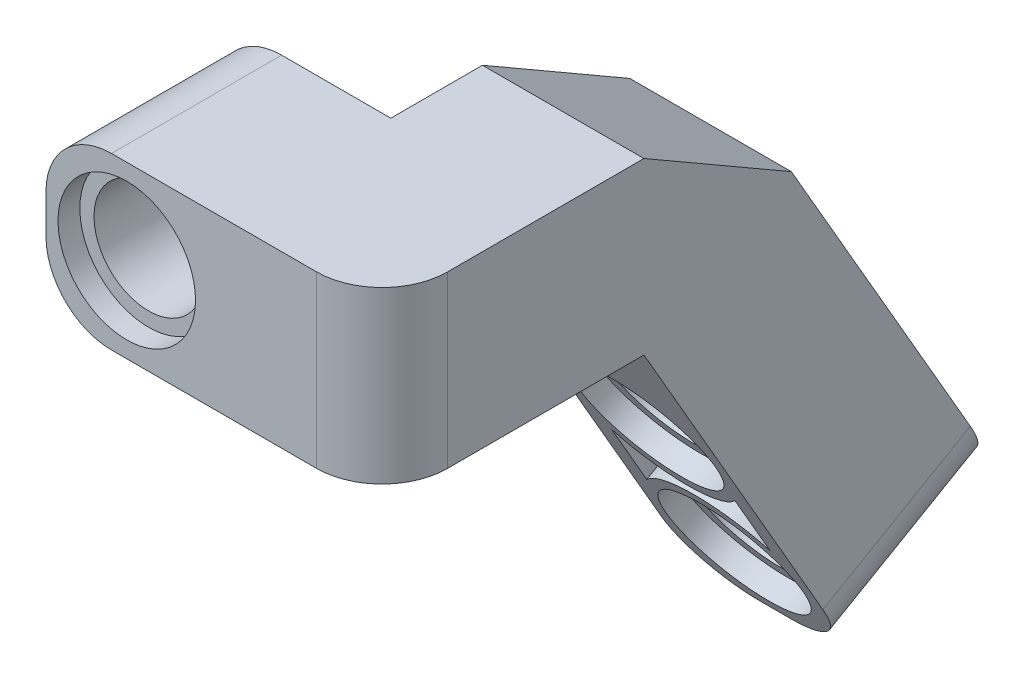
SolidWorks part; units mm, degrees
ref_plane "前视基准面" through (0, 0, 0) normal (0, 0, 1) x (1, 0, 0)
ref_plane "上视基准面" through (0, 0, 0) normal (0, 1, 0) x (1, 0, 0)
ref_plane "右视基准面" through (0, 0, 0) normal (1, 0, 0) x (0, 0, -1)
other "Configuration Table"
sketch "草图1" plane through (0, 0, 0) normal (1, 0, 0) x (0, 0, -1)
  line L0 (0, 7.8) -> (6.755, 3.9)
  line L1 (-12, 7.8) -> (0, 7.8)
  line L2 (-12, 7.8) -> (-12, 0)
  line L3 (-12, 0) -> (0, 0)
  line L4 (0, 7.8) -> (0, 0)
  line L9 (0, 0) -> (9.7, -16.8009)
  line L10 (0, 0) -> (6.755, 3.9)
  line L11 (6.755, 3.9) -> (16.455, -12.9009)
  line L12 (9.7, -16.8009) -> (16.455, -12.9009)
  dimension "D1" = 240
  dimension "D2" = 7.8
  dimension "D3" = 7.8
  dimension "D4" = 19.4
  dimension "D5" = 12
extrude "凸台-拉伸1" add sketch "草图1" along normal blind 7.4 contours L4 L1 L2 L3 | L4 L10 L0 | L9 L12 L11 L10 region at (0, 3.9, 6) region at (0, 3.9, -2.2517) region at (0, -6.4504, -8.2275)
sketch "草图2" plane through (0, 7.8, 0) normal (0, 1, 0) x (1, 0, 0)
  line L0 (3.7, 0) -> (3.7, -12) construction
  line L1 (-8, -4.2) -> (-0.6, -4.2)
  line L2 (-8, -4.2) -> (-8, -12)
  line L3 (-8, -12) -> (-0.6, -12)
  line L4 (-0.6, -4.2) -> (-0.6, -12)
  line L5 (7.4, 0) -> (0, 0) construction
  line L6 (7.4, -12) -> (0, -12) construction
  line L7 (-4.3, -4.2) -> (-4.3, -12) construction
  line L8 (-0.6, -4.2) -> (0, -4.2)
  line L9 (0, -12) -> (0, 0) construction
  line L10 (-0.6, -12) -> (0, -12)
  line M7 (0, 0) -> (0, -12)
  dimension "D1" = 8
  dimension "D2" = 7.8
  dimension "D3" = 7.4
extrude "凸台-拉伸2" add sketch "草图2" against normal blind 7.8 contours L4 L10 L8 M7 | L4 L1 L2 L3 region at (-4.3, 7.8, 8.1) region at (-0.3, 7.8, 8.1)
sketch "草图4" plane through (0, 0, 4.2) normal (0, 0, -1) x (-1, 0, 0)
  line L0 (4.3, 0) -> (4.3, 7.8) construction
  line L1 (8, 7.8) -> (0.6, 7.8)
  line L2 (8, 7.8) -> (8, 0)
  line L3 (8, 0) -> (0.6, 0)
  line L4 (0.6, 7.8) -> (0.6, 0)
  line L5 (8, 0) -> (0, 0) construction
  line L6 (8, 3.9) -> (0.6, 3.9) construction
  circle A0 centre (4.3, 3.9) radius 2.5
  circle A1 centre (4.3, 3.9) radius 3.15
  circle A2 centre (4.3, 3.9) radius 3.7
  dimension "D2" = 7.4
  dimension "D3" = 6.3
  dimension "D4" = 5
  dimension "D1" = 7.4
extrude "切除-拉伸1" cut sketch "草图4" against normal up to next contours A0 region at (-4.3, 3.9, 4.2)
extrude "切除-拉伸2" cut sketch "草图4<3>" against normal blind 1 contours A1 A0 region at (-1.2391, 3.9, 4.2)
sketch "草图4<3>" plane through (0, 0, 4.2) normal (0, 0, -1) x (-1, 0, 0) same geometry as "草图4"
extrude "切除-拉伸3" cut sketch "草图4<4>" along normal blind 1 from surface contours A1 A0 region at (-1.2391, 3.9, 4.2) starting at face at (-4.3, 6.4, 12)
sketch "草图4<4>" plane through (0, 0, 4.2) normal (0, 0, -1) x (-1, 0, 0) same geometry as "草图4"
sketch "草图5" plane through (0, 3.9, -6.755) normal (0, 0.5, -0.866) x (1, 0, 0)
  line L0 (3.7, 19.4) -> (3.7, 0) construction
  line L1 (7.4, 19.4) -> (0, 19.4) construction
  line L2 (7.4, 0) -> (0, 0) construction
  line L3 (0, 9.7) -> (7.4, 9.7)
  line L4 (0, 0) -> (0, 19.4) construction
  line L5 (7.4, 0) -> (7.4, 19.4) construction
  circle A0 centre (3.7, 15.7) radius 2.5
  circle A2 centre (3.7, 15.7) radius 3.15
  circle A3 centre (3.7, 15.7) radius 3.7
  dimension "D2" = 7.4
  dimension "D3" = 6.3
  dimension "D4" = 5
  dimension "D1" = 6
extrude "切除-拉伸4" cut sketch "草图5" against normal blind 1 contours L0 A2 A0 | A2 L0 A0 region at (5.8776, -11.5824, -15.6938) region at (3.6296, -12.1431, -16.0175)
extrude "切除-拉伸5" cut sketch "草图5<3>" along normal blind 1 from surface contours L0 A2 A0 | A2 L0 A0 region at (5.8776, -11.5824, -15.6938) region at (3.6296, -12.1431, -16.0175) starting at face at (3.7, -8.4004, -4.85)
sketch "草图5<3>" plane through (0, 3.9, -6.755) normal (0, 0.5, -0.866) x (1, 0, 0) same geometry as "草图5"
extrude "切除-拉伸6" cut sketch "草图5<4>" against normal up to next contours L0 A0 | A0 L0 region at (4.761, -9.6966, -14.605) region at (2.639, -9.6966, -14.605)
sketch "草图5<4>" plane through (0, 3.9, -6.755) normal (0, 0.5, -0.866) x (1, 0, 0) same geometry as "草图5"
pattern_linear "阵列(线性)1" count 2 spacing 8 along (0, 0.866, 0.5) of "切除-拉伸4", "切除-拉伸5", "切除-拉伸6"
sketch "草图6" plane through (0, 3.9, -6.755) normal (0, 0.5, -0.866) x (1, 0, 0)
  line L0 (3.7, 19.4) -> (3.7, 0) construction
  line L1 (7.4, 19.4) -> (0, 19.4) construction
  line L2 (7.4, 0) -> (0, 0) construction
  line L3 (0, 9.7) -> (7.4, 9.7) construction
  line L4 (0, 0) -> (0, 19.4) construction
  line L5 (7.4, 0) -> (7.4, 19.4) construction
  line L6 (6.2, 15.7) -> (6.85, 15.7)
  line L7 (1.2, 15.7) -> (0.55, 15.7)
  line L8 (0.875, 15.7) -> (0.875, 10.0894)
  line L9 (6.525, 15.7) -> (6.525, 10.0894)
  circle A0 centre (3.7, 15.7) radius 2.5
  circle A1 centre (3.7, 15.7) radius 3.15
  circle A2 centre (3.7, 15.7) radius 3.7
  circle A3 centre (3.7, 7.7) radius 3.7
  dimension "D2" = 7.4
  dimension "D3" = 6.3
  dimension "D4" = 5
  dimension "D1" = 6
  dimension "D5" = 8
extrude "切除-拉伸7" cut sketch "草图6" against normal blind 2 contours A3 L9 A2 L8 region at (3.7, -6.2325, -12.605)
extrude "切除-拉伸8" cut sketch "草图6<3>" along normal blind 2 from surface contours A3 L9 A2 L8 region at (3.7, -6.2325, -12.605) starting at face at (3.7, -3.9404, -2.275)
sketch "草图6<3>" plane through (0, 3.9, -6.755) normal (0, 0.5, -0.866) x (1, 0, 0) same geometry as "草图6"
fillet "圆角1" radius 3 5 edges at (7.4, 3.9, 12) (-8, 7.8, 8.1) (-8, 0, 8.1) (0, -14.8509, -13.0775) (7.4, -14.8509, -13.0775)
pattern_linear "阵列(线性)4" count 2 spacing 8 along (0, 0.866, 0.5) of "切除-拉伸7"
